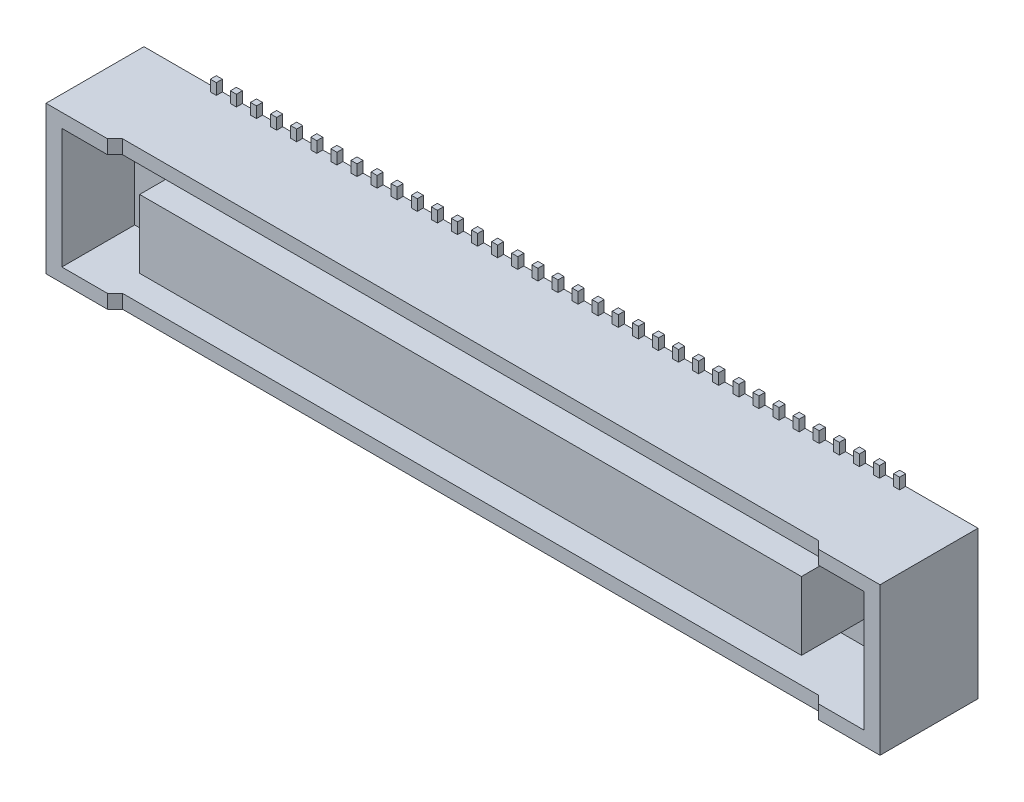
SolidWorks part; units mm, degrees
ref_plane "Front Plane" through (0, 0, 0) normal (0, 0, 1) x (1, 0, 0)
ref_plane "Top Plane" through (0, 0, 0) normal (0, 1, 0) x (1, 0, 0)
ref_plane "Right Plane" through (0, 0, 0) normal (1, 0, 0) x (0, 0, -1)
sketch "Sketch1" plane through (0, 0, 0) normal (0, 1, 0) x (1, 0, 0)
  line L0 (0, 0) -> (-8.3, 0)
  line L1 (-8.3, 0) -> (-8.3, -1.95)
  line L2 (-8.3, -1.95) -> (-7.0768, -1.95)
  line L3 (-7.0768, -1.95) -> (-6.9268, -1.8)
  line L4 (-6.9268, -1.8) -> (0, -1.8)
  line L5 (0, -1.8) -> (0, 0)
  point P3 (-11.1611, -1.8)
  point P8 (-11.3323, -1.95)
  dimension "D1" = 1.95
  dimension "D2" = 1.8
  dimension "D3" = 135
  dimension "D4" = 8.3
extrude "Boss-Extrude1" add sketch "Sketch1" along normal blind 1.47 and the other way blind 1.47
mirror "Mirror1" about plane through (0, 0, 0) normal (1, 0, 0) of "Boss-Extrude1"
sketch "Sketch2" plane through (0, 0, 1.8) normal (0, 0, 1) x (1, 0, 0)
  line L1 (7.9845, -1.1952) -> (-7.9845, -1.1952)
  line L2 (7.9845, -1.1952) -> (7.9845, 1.1952)
  line L3 (7.9845, 1.1952) -> (-7.9845, 1.1952)
  line L4 (-7.9845, -1.1952) -> (-7.9845, 1.1952)
  line L5 (7.9845, -1.1952) -> (-7.9845, 1.1952) construction
  line L6 (7.9845, 1.1952) -> (-7.9845, -1.1952) construction
  line L7 (6.586, 0.6799) -> (-6.586, 0.6799)
  line L8 (6.586, 0.6799) -> (6.586, -0.6799)
  line L9 (6.586, -0.6799) -> (-6.586, -0.6799)
  line L10 (-6.586, 0.6799) -> (-6.586, -0.6799)
  line L11 (6.586, 0.6799) -> (-6.586, -0.6799) construction
  line L12 (6.586, -0.6799) -> (-6.586, 0.6799) construction
  point P0 (0, 0)
  point P6 (0, 0)
extrude "Cut-Extrude1" cut sketch "Sketch2" against normal blind 1.3 and the other way through all
sketch "Sketch3" plane through (0, -1.47, 0) normal (0, -1, 0) x (-1, 0, 0)
  line L0 (-8.3, 0) -> (8.3, 0) construction
  line L1 (6.86, 0) -> (6.74, 0)
  line L2 (6.86, 0) -> (6.86, -0.12)
  line L3 (6.86, -0.12) -> (6.74, -0.12)
  line L4 (6.74, 0) -> (6.74, -0.12)
  line L5 (6.86, -0.12) -> (6.74, 0) construction
  line L6 (6.74, -0.12) -> (6.86, 0) construction
  point P6 (6.8, -0.06)
  dimension "D1" = 6.8
  dimension "D2" = 0.12
  dimension "D3" = 0.12
extrude "Boss-Extrude2" add sketch "Sketch3" along normal blind 0.22
pattern_linear "LPattern1" count 35 spacing 0.4 along (1, 0, 0) of "Boss-Extrude2"
mirror "Mirror2" about plane through (0, 0, 0) normal (0, 1, 0) of "LPattern1"
